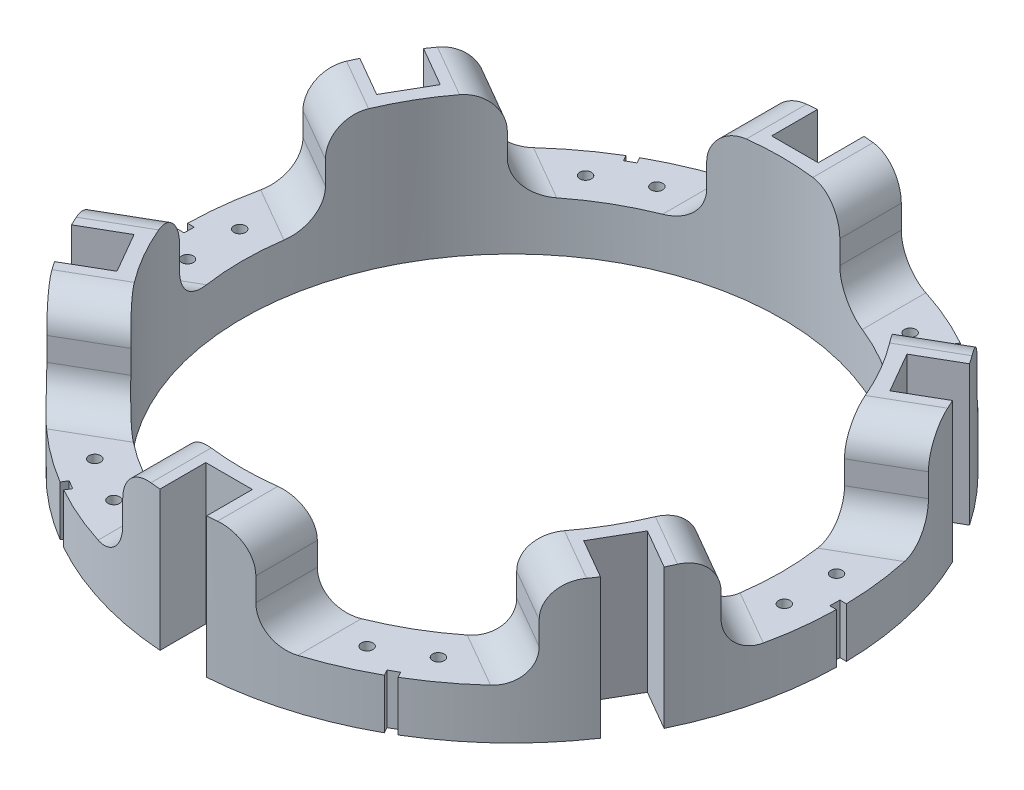
SolidWorks part; units mm, degrees
ref_plane "Спереди" through (0, 0, 0) normal (0, 0, 1) x (1, 0, 0)
ref_plane "Сверху" through (0, 0, 0) normal (0, 1, 0) x (1, 0, 0)
ref_plane "Справа" through (0, 0, 0) normal (1, 0, 0) x (0, 0, -1)
sketch "Эскиз1" plane through (0, 0, 0) normal (0, 1, 0) x (1, 0, 0)
  circle A0 centre (0, 0) radius 81
  circle A1 centre (0, 0) radius 99
  dimension "D1" = 198
  dimension "D2" = 162
extrude "Бобышка-Вытянуть1" add sketch "Эскиз1" along normal blind 15
sketch "Эскиз2" plane through (0, 15, 0) normal (0, 1, 0) x (1, 0, 0)
  line L0 (0, 0) -> (0, 92) construction
  line L1 (-7, 99) -> (7, 99)
  line L2 (-7, 99) -> (-7, 85)
  line L3 (-7, 85) -> (7, 85)
  line L4 (7, 99) -> (7, 85)
  line L5 (-7, 99) -> (7, 85) construction
  line L6 (-7, 85) -> (7, 99) construction
  circle A0 centre (0, 0) radius 99 construction
  point P0 (0, 92)
  dimension "D1" = 14
  dimension "D2" = 14
ref_plane "Плоскость1" through (0, 0, -99) normal (0, 0, -1) x (-1, 0, 0)
sketch "Эскиз5" plane through (0, 15, 0) normal (0, 1, 0) x (1, 0, 0)
  line L0 (-20, 78.492) -> (-20, 96.9588)
  line L1 (20, 78.492) -> (20, 96.9588)
  line L3 (0, 92) -> (-20, 92) construction
  line L4 (-7, 99) -> (7, 85) construction
  line L5 (0, 92) -> (20, 92) construction
  arc A0 (-20, 78.492) -> (20, 78.492) centre (0, 0) cw
  circle A1 centre (0, 0) radius 81 construction
  arc A2 (-20, 96.9588) -> (20, 96.9588) centre (0, 0) cw
  circle A3 centre (0, 0) radius 99 construction
  dimension "D1" = 40
extrude "Бобышка-Вытянуть2" add sketch "Эскиз5" along normal blind 27
extrude "Вырез-Вытянуть2" cut sketch "Эскиз2" along normal through all and the other way through all contours L3 L4 L1 L2
fillet "Скругление1" radius 10 4 edges at (-20, 15, -87.7254) (-20, 42, -87.7254) (20, 15, -87.7254) (20, 42, -87.7254)
pattern_circular "Круговой массив2" count 6 over 360 about axis through (0, 15, 0) along (0, 1, 0) of "Скругление1", "Вырез-Вытянуть2", "Бобышка-Вытянуть2"
sketch "Эскиз6" plane through (0, 15, 0) normal (0, 1, 0) x (1, 0, 0)
  line L0 (0, 0) -> (-45, 77.9423) construction
  line L1 (0, 0) -> (0, 92) construction
  line L2 (-45, 77.9423) -> (-48.5058, 84.0145) construction
  line L3 (-49.8163, 83.2847) -> (-47.1953, 84.7443)
  line L4 (-50.7894, 85.032) -> (-48.1684, 86.4916)
  line L5 (-49.8163, 83.2847) -> (-50.7894, 85.032)
  line L6 (-47.1953, 84.7443) -> (-48.1684, 86.4916)
  line L7 (0, 0) -> (-38.0356, 81.5677) construction
  line L8 (0, 0) -> (-51.6219, 73.7237) construction
  circle A0 centre (0, 0) radius 90 construction
  arc A2 (-30, 94.3451) -> (-66.7053, 73.1533) centre (0, 0) ccw construction
  circle A3 centre (-51.6219, 73.7237) radius 1.75
  circle A4 centre (-38.0356, 81.5677) radius 1.75
  point P14 (-48.5058, 84.0145)
  point P17 (-49.4789, 85.7618)
  dimension "D1" = 180
  dimension "D3" = 10
  dimension "D7" = 3.5
  dimension "D8" = 3.5
  dimension "D2" = 30
  dimension "D4" = 3
  dimension "D5" = 2
  dimension "D6" = 5
extrude "Вырез-Вытянуть3" cut sketch "Эскиз6" against normal through all
pattern_circular "Круговой массив3" count 6 over 360 about axis through (0, 15, 0) along (0, 1, 0) of "Вырез-Вытянуть3"
